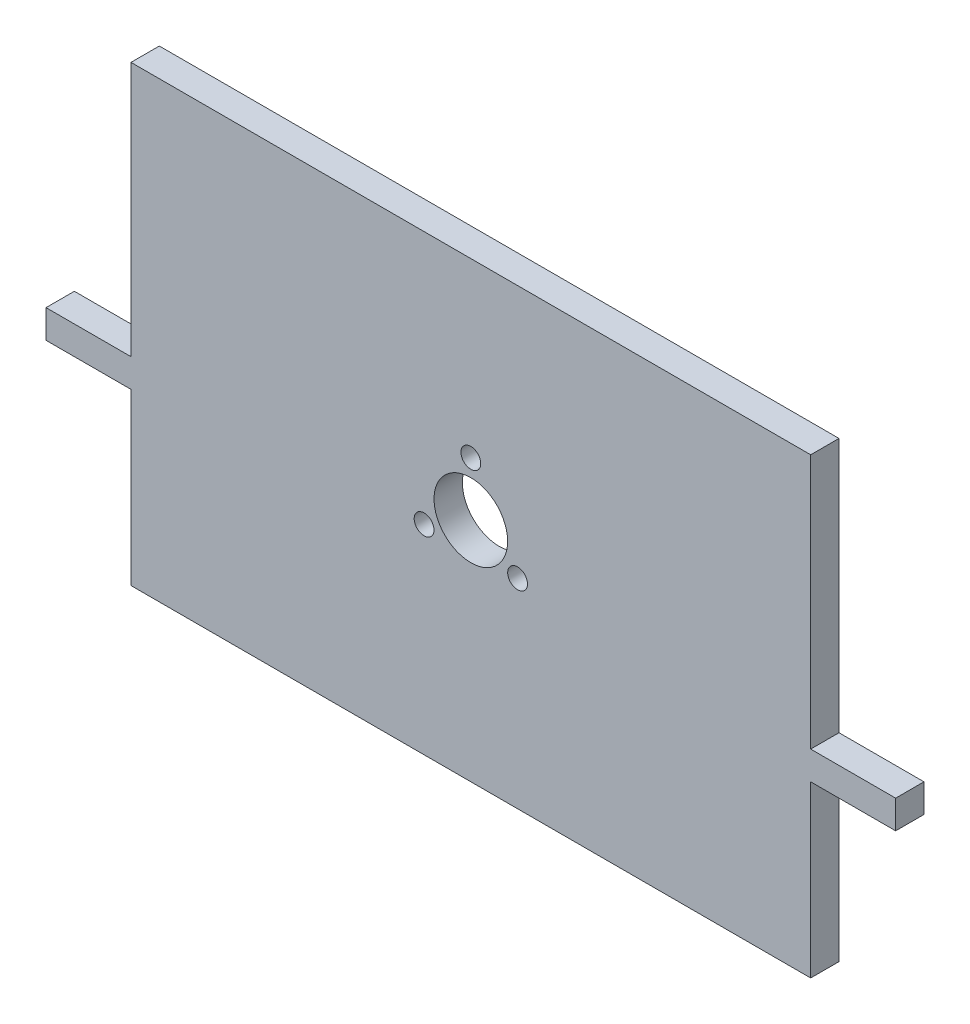
SolidWorks part; units mm, degrees
ref_plane "前视基准面" through (0, 0, 0) normal (0, 0, 1) x (1, 0, 0)
ref_plane "上视基准面" through (0, 0, 0) normal (0, 1, 0) x (1, 0, 0)
ref_plane "右视基准面" through (0, 0, 0) normal (1, 0, 0) x (0, 0, -1)
other "Configuration Table"
sketch "草图1" plane through (0, 0, 0) normal (0, 0, 1) x (1, 0, 0)
  line L1 (60, -45) -> (-60, -45)
  line L2 (60, -45) -> (60, 45)
  line L3 (60, 45) -> (-60, 45)
  line L4 (-60, -45) -> (-60, 45)
  line L5 (60, -45) -> (-60, 45) construction
  line L6 (60, 45) -> (-60, -45) construction
  point P0 (0, 0)
  dimension "D1" = 120
  dimension "D2" = 90
extrude "凸台-拉伸1" add sketch "草图1" along normal blind 5
sketch "草图5" plane through (0, 0, 0) normal (0, 0, -1) x (-1, 0, 0)
  line L0 (60, 45) -> (60, -45) construction
  line L1 (-60, -45) -> (60, -45)
  line L2 (-60, -45) -> (-60, -35)
  line L3 (-60, -35) -> (60, -35)
  line L4 (60, -45) -> (60, -35)
  dimension "D1" = 10
extrude "切除-拉伸3" cut sketch "草图5" against normal blind 10
sketch "草图8" plane through (60, 0, 0) normal (1, 0, 0) x (0, 0, -1)
  line L0 (0, 0.0974) -> (0, -5.0026)
  line L1 (0, -35) -> (0, 45) construction
  line L2 (-38.4322, 0.0974) -> (59.5678, 0.0974) construction
  line L3 (59.5678, -5.0026) -> (-38.4322, -5.0026) construction
  line L4 (0, -5.0026) -> (-5, -5.0026)
  line L5 (-5, -35) -> (-5, 45) construction
  line L6 (-5, -5.0026) -> (-5, 0.0974)
  line L7 (-5, 0.0974) -> (0, 0.0974)
  line L9 (-4.95, -5.0026) -> (-0.05, -5.0026)
  line L10 (-4.95, -5.0026) -> (-4.95, 0.0974)
  line L11 (-4.95, 0.0974) -> (-0.05, 0.0974)
  line L12 (-0.05, -5.0026) -> (-0.05, 0.0974)
  line L13 (-4.95, -5.0026) -> (-0.05, 0.0974) construction
  line L14 (-4.95, 0.0974) -> (-0.05, -5.0026) construction
  point P8 (-2.5, -2.4526)
  dimension "D1" = 0.05
  dimension "D2" = 0.05
  dimension "D3" = 0
  dimension "D4" = 0
sketch "草图10" plane through (60, 0, 0) normal (1, 0, 0) x (0, 0, -1)
  line L0 (-5, -35) -> (-5, 45) construction
  line L1 (0, 0) -> (-5, 0)
  line L2 (-5, 0) -> (-5, -5.0026)
  line L3 (-5, -5.0026) -> (0, -5.0026)
  line L4 (0, -35) -> (0, 45) construction
  line L5 (0, -5.0026) -> (0, 0)
extrude "凸台-拉伸3" add sketch "草图10" along normal blind 15
sketch "草图11" plane through (0, 0, 0) normal (0, 0, -1) x (-1, 0, 0)
  line L0 (0, 45) -> (0, -35) construction
  line L1 (-60, 45) -> (60, 45) construction
  line L2 (60, -35) -> (-60, -35) construction
sketch "草图12" plane through (-60, 0, 0) normal (-1, 0, 0) x (0, 0, 1)
  line L4 (0, 45) -> (0, -35)
  line L5 (0, -35) -> (5, -35)
  line L6 (5, -35) -> (5, 45)
  line L7 (5, 45) -> (0, 45)
  line L8 (0, 45) -> (0, -35)
  line L9 (0, -35) -> (5, -35)
  line L10 (5, -35) -> (5, 45)
  line L11 (5, 45) -> (0, 45)
  line L12 (0, 0) -> (0, -5.0026)
  line L13 (5, 0) -> (0, 0)
  line L14 (5, -5.0026) -> (5, 0)
  line L15 (0, -5.0026) -> (5, -5.0026)
  line L16 (0, 0) -> (0, -5.0026)
  line L17 (5, 0) -> (0, 0)
  line L18 (5, -5.0026) -> (5, 0)
  line L19 (0, -5.0026) -> (5, -5.0026)
  dimension "D1" = 0
  dimension "D2" = 0
extrude "凸台-拉伸4" add sketch "草图12" along normal blind 15 contours L8 L19 L10 L17 region at (-60, -2.5013, 2.5)
sketch "草图13" plane through (0, 0, 5) normal (0, 0, 1) x (1, 0, 0)
  line L0 (-60, 45) -> (60, -35) construction
  line L1 (60, 45) -> (-60, -35) construction
  circle A0 centre (0, 5) radius 6.5
  circle A1 centre (8.2532, 0.235) radius 1.75
  circle A2 centre (-8.2532, 0.235) radius 1.75
  circle A3 centre (0, 5) radius 9.53
  circle A4 centre (0, 14.53) radius 1.75
  point P19 (0, 5)
  dimension "D1" = 13
  dimension "D2" = 19.06
  dimension "D3" = 3.5
  dimension "D4" = 3
extrude "切除-拉伸4" cut sketch "草图13" against normal blind 15 contours A0 | A3 A4 | A3 A4 | A3 A2 | A2 A3 | A3 A1 | A1 A3 region at (0, 5, 5) region at (8.8707, -0.1215, 5) region at (7.5856, 0.6205, 5) region at (-7.5856, 0.6205, 5) region at (-8.8707, -0.1215, 5) region at (0, 13.7591, 5) region at (0, 15.243, 5)
